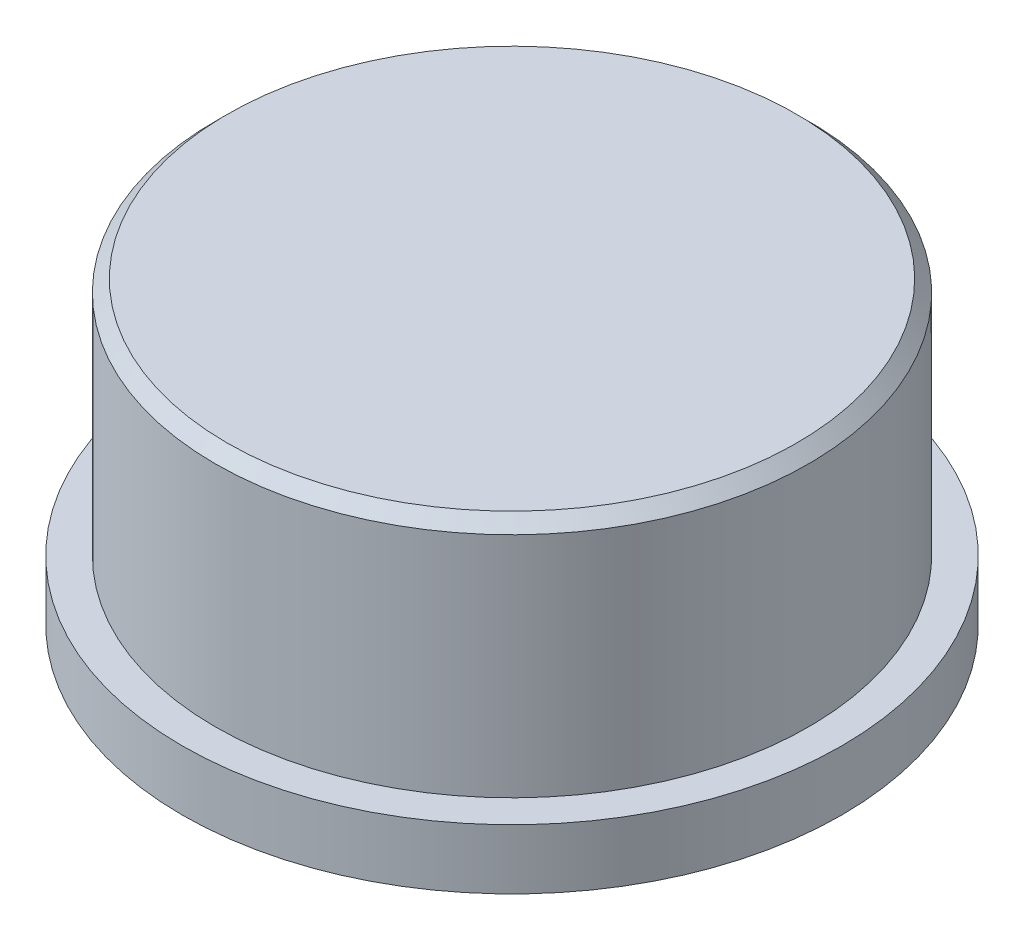
SolidWorks part; units mm, degrees
material "ABS"
ref_plane "Front Plane" through (0, 0, 0) normal (0, 0, 1) x (1, 0, 0)
ref_plane "Top Plane" through (0, 0, 0) normal (0, 1, 0) x (1, 0, 0)
ref_plane "Right Plane" through (0, 0, 0) normal (1, 0, 0) x (0, 0, -1)
sketch "Sketch1" plane through (0, 0, 0) normal (0, 1, 0) x (1, 0, 0)
  circle A0 centre (0, 0) radius 5.5
  dimension "D1" = 11
extrude "Boss-Extrude1" add sketch "Sketch1" along normal blind 1
sketch "Sketch2" plane through (0, 1, 0) normal (0, 1, 0) x (1, 0, 0)
  circle A0 centre (0, 0) radius 4.95
  dimension "D1" = 9.9
extrude "Boss-Extrude2" add sketch "Sketch2" along normal blind 4
sketch "Sketch3" plane through (0, 0, 0) normal (0, -1, 0) x (1, 0, 0)
  line L1 (2.9445, 0) -> (1.4722, 2.55)
  line L2 (1.4722, 2.55) -> (-1.4722, 2.55)
  line L3 (-1.4722, 2.55) -> (-2.9445, 0)
  line L4 (-2.9445, 0) -> (-1.4722, -2.55)
  line L5 (-1.4722, -2.55) -> (1.4722, -2.55)
  line L6 (1.4722, -2.55) -> (2.9445, 0)
  circle A0 centre (0, 0) radius 2.55 construction
  dimension "D1" = 5.1
extrude "Cut-Extrude1" cut sketch "Sketch3" against normal blind 4 contours L1 L2 L3 L4 L5 L6
chamfer "Chamfer1" distance 0.2 angle 45 1 edges at (0, 5, 4.95)
